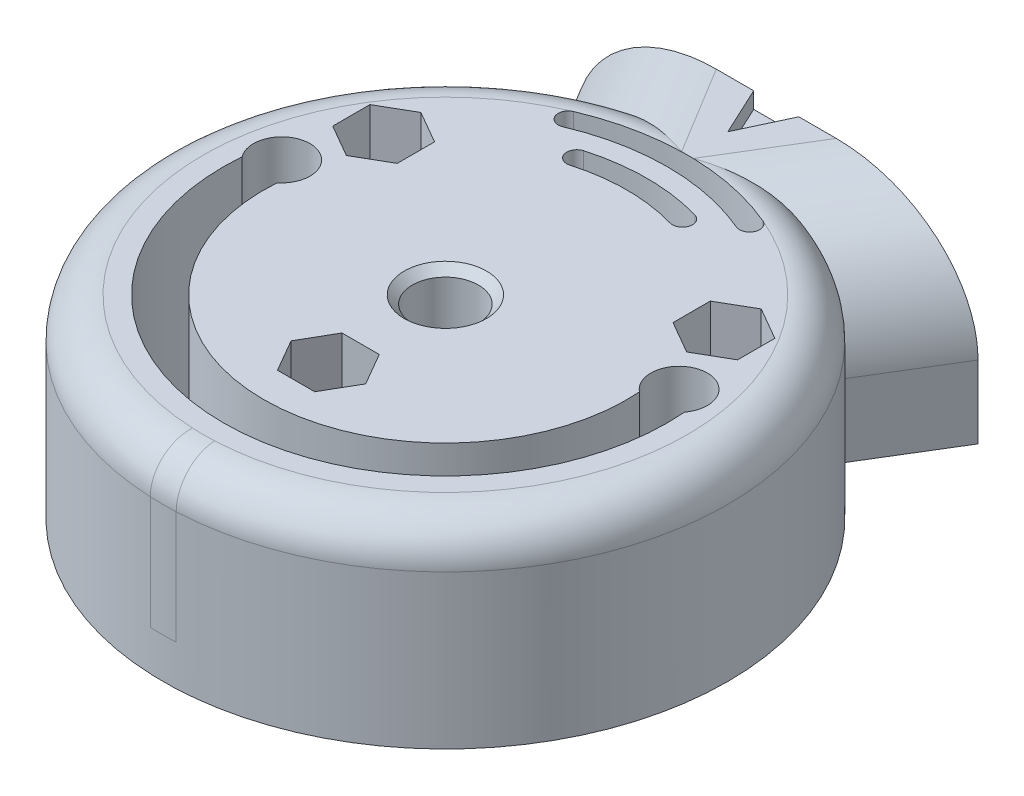
SolidWorks part; units mm, degrees
ref_plane "Alzado" through (0, 0, 0) normal (0, 0, 1) x (1, 0, 0)
ref_plane "Planta" through (0, 0, 0) normal (0, 1, 0) x (1, 0, 0)
ref_plane "Vista lateral" through (0, 0, 0) normal (1, 0, 0) x (0, 0, -1)
sketch "Croquis1" plane through (0, 0, 0) normal (0, 1, 0) x (1, 0, 0)
  line L0 (0, 35) -> (0, 41) construction
  line L1 (-35, 0) -> (-35, 35) construction
  line L2 (35, 0) -> (35, 35) construction
  line L3 (-35, 35) -> (35, 35) construction
  line L4 (0, 38) -> (-35, 38) construction
  line L5 (-35, 38) -> (35, 38) construction
  line L6 (35, 38) -> (35, 35) construction
  line L7 (-35, 38) -> (-35, 35) construction
  line L8 (0, 41) -> (-35, 41) construction
  line L9 (-35, 41) -> (-35, 38) construction
  line L10 (-25, 41) -> (25, 41)
  line L11 (-25, 41) -> (-18.2213, 29.8829)
  line L12 (25, 41) -> (18.2213, 29.8829)
  circle A0 centre (0, 0) radius 35
  circle A1 centre (0, 0) radius 4.1
  point P3 (0, 35)
  dimension "D1" = 70
  dimension "D4" = 8.2
  dimension "D2" = 6
  dimension "D3" = 50
  dimension "D5" = 11.1171
extrude "Saliente-Extruir1" add sketch "Croquis1" along normal blind 24 contours A0 | A0 L10 region at (0, 0, -37.0825) region at (0, 0, -34.0101)
sketch "Croquis2" plane through (0, 24, 0) normal (0, 1, 0) x (1, 0, 0)
  line L0 (0, 41) -> (0, -35) construction
  line L1 (-25, 41) -> (25, 41) construction
  line L2 (0, -33.75) -> (1.05, -33.75)
  line L3 (0, -33.75) -> (-1.05, -33.75)
  line L4 (-1.05, -33.75) -> (-1.55, -33.75) construction
  line L5 (1.05, -33.75) -> (1.55, -33.75) construction
  line L6 (-1.55, -33.75) -> (-1.6057, -34.9631) construction
  line L7 (1.55, -33.75) -> (1.6057, -34.9631) construction
  line L8 (-1.05, -33.75) -> (-1.6057, -34.9631)
  line L9 (1.05, -33.75) -> (1.6057, -34.9631)
  line L10 (-1.6057, -34.9631) -> (-3.3557, -34.8828) construction
  arc A0 (-18.2213, 29.8829) -> (18.2213, 29.8829) centre (0, 0) ccw construction
  circle A1 centre (0, 0) radius 33.75
  circle A2 centre (0, 0) radius 35
  arc M1 (-18.2213, 29.8829) -> (18.2213, 29.8829) centre (0, 0) ccw
  dimension "D1" = 1.25
  dimension "D2" = 2.1
  dimension "D3" = 0.5
  dimension "D4" = 0.5
  dimension "D5" = 1.75
extrude "Cortar-Extruir1" cut sketch "Croquis2" against normal blind 19 contours L9 L2 L3 L8 M1 region at (0, 24, 34.4127)
sketch "Croquis12" plane through (0, 0, -41) normal (0, 0, -1) x (-1, 0, 0)
  line L0 (0, 24) -> (0, 0) construction
  line L1 (25, 24) -> (-25, 24) construction
  line L3 (0, 12) -> (15, 12)
  line L7 (0, 12) -> (-15, 12)
  circle A0 centre (-15, 12) radius 1.65
  circle A1 centre (15, 12) radius 1.65
  dimension "D3" = 3.3
  dimension "D1" = 30
  dimension "D2" = 12
sketch "Croquis13" plane through (0, 0, 0) normal (0, -1, 0) x (1, 0, 0)
  line L0 (25, -41) -> (15, -41) construction
  line L1 (-25, -41) -> (25, -41) construction
  line L2 (15, -41) -> (15, -35) construction
  line L3 (15, -35) -> (11.6, -35) construction
  line L4 (15, -35) -> (18.4, -35) construction
  line L5 (18.4, -35) -> (11.6, -35)
  line L6 (18.4, -35) -> (18.4, -32.1)
  line L7 (18.4, -32.1) -> (11.6, -32.1)
  line L8 (11.6, -32.1) -> (11.6, -35)
  line L9 (0, -41) -> (0, 0) construction
  line L10 (-15, -35) -> (-18.4, -35) construction
  line L11 (-15, -35) -> (-11.6, -35) construction
  line L12 (-11.6, -32.1) -> (-11.6, -35)
  line L13 (-18.4, -32.1) -> (-11.6, -32.1)
  line L14 (-18.4, -35) -> (-18.4, -32.1)
  line L15 (-18.4, -35) -> (-11.6, -35)
  dimension "D1" = 10
  dimension "D2" = 6
  dimension "D3" = 6.8
  dimension "D4" = 2.9
sketch "Croquis8" plane through (0, 24, 0) normal (0, 1, 0) x (1, 0, 0)
  line L0 (0, 0) -> (0, 41) construction
  line L1 (0, 0) -> (-18.4123, 30.6439)
  line L2 (0, 0) -> (18.4123, 30.6439)
  line L9 (-1.6057, -34.9631) -> (-1.05, -33.75)
  line L10 (-1.6057, -34.9631) -> (-1.05, -33.75)
  line L11 (-1.05, -33.75) -> (1.05, -33.75)
  line L12 (-1.05, -33.75) -> (1.05, -33.75)
  line L13 (1.05, -33.75) -> (1.6057, -34.9631)
  line L14 (1.05, -33.75) -> (1.6057, -34.9631)
  line L15 (18.2213, 29.8829) -> (25, 41)
  line L16 (18.2213, 29.8829) -> (25, 41)
  line L17 (25, 41) -> (-25, 41)
  line L18 (25, 41) -> (-25, 41)
  line L19 (-25, 41) -> (-18.2213, 29.8829)
  line L20 (-25, 41) -> (-18.2213, 29.8829)
  circle A0 centre (0, 0) radius 35.75
  circle A1 centre (0, 0) radius 33.25
  arc A3 (-18.2213, 29.8829) -> (-1.6057, -34.9631) centre (0, 0) ccw
  arc A4 (-18.2213, 29.8829) -> (-1.6057, -34.9631) centre (0, 0) ccw
  arc A6 (1.6057, -34.9631) -> (18.2213, 29.8829) centre (0, 0) ccw
  arc A7 (1.6057, -34.9631) -> (18.2213, 29.8829) centre (0, 0) ccw
  dimension "D1" = 71.5
  dimension "D2" = 66.5
  dimension "D4" = 30.6439
  dimension "D3" = 0
extrude "Saliente-Extruir3" add sketch "Croquis8" against normal up to surface (24 mm away) contours A1 L0 A0 L1 | L0 A1 L2 A0 region at (-9.1115, 24, -32.8557) region at (9.1115, 24, -32.8557) up to face at (0, 0, 4.1)
fillet "Redondeo7" radius 15 2 edges at (21.6106, 24, -35.4414) (-21.6106, 24, -35.4414)
sketch "Croquis10" plane through (0, 24, 0) normal (0, 1, 0) x (1, 0, 0)
  line L0 (0, 41) -> (0, -35) construction
  line L1 (-7.4314, 41) -> (7.4314, 41) construction
  line L2 (0, 0) -> (-10.7451, 25.3139) construction
  line L3 (-10.7451, 25.3139) -> (-11.7219, 27.6151) construction
  line L4 (10.7451, 25.3139) -> (11.7219, 27.6151) construction
  line L5 (-8.7915, 20.7114) -> (-9.7683, 23.0126) construction
  line L6 (-8.7915, 20.7114) -> (-9.7683, 23.0126) construction
  line L7 (-8.7915, 20.7114) -> (-9.7683, 23.0126)
  line L8 (0, 0) -> (6.1996, 21.629) construction
  line L9 (6.1996, 21.629) -> (6.8885, 24.0323) construction
  line L10 (-6.1996, 21.629) -> (-6.8885, 24.0323) construction
  circle A0 centre (0, 0) radius 30
  circle A1 centre (0, 0) radius 27.5
  arc A2 (-1.6057, -34.9631) -> (1.6057, -34.9631) centre (0, 0) ccw construction
  arc A3 (-11.7219, 27.6151) -> (-10.7451, 25.3139) centre (-11.2335, 26.4645) ccw
  arc A4 (11.7219, 27.6151) -> (10.7451, 25.3139) centre (11.2335, 26.4645) cw
  circle A5 centre (0, 0) radius 25
  circle A6 centre (0, 0) radius 22.5
  arc A7 (6.1996, 21.629) -> (6.8885, 24.0323) centre (6.544, 22.8306) ccw
  arc A8 (-6.1996, 21.629) -> (-6.8885, 24.0323) centre (-6.544, 22.8306) cw
  point P19 (-8.7915, 20.7114)
  dimension "D1" = 60
  dimension "D2" = 55
  dimension "D4" = 50
  dimension "D5" = 45
  dimension "D3" = 23
extrude "Cortar-Extruir5" cut sketch "Croquis10" against normal blind 29 contours A4 A0 A3 A1 | A8 A6 A7 A5 region at (0, 24, -23.3638) region at (0, 24, -27.8649)
sketch "Croquis11" plane through (0, 24, 0) normal (0, 1, 0) x (1, 0, 0)
  line L0 (-21.1734, 3.7334) -> (-22.1582, 3.9071) construction
  line L2 (0, 0) -> (0, -35) construction
  arc A0 (-27.4097, 2.2272) -> (27.4097, 2.2272) centre (0, 0) ccw
  arc A1 (-22.443, 1.6008) -> (22.443, 1.6008) centre (0, 0) ccw
  arc A2 (-1.6057, -34.9631) -> (1.6057, -34.9631) centre (0, 0) ccw construction
  arc A3 (-22.443, 1.6008) -> (-27.4097, 2.2272) centre (-24.6202, 4.3412) ccw
  arc A4 (22.443, 1.6008) -> (27.4097, 2.2272) centre (24.6202, 4.3412) cw
  dimension "D1" = 55
  dimension "D2" = 45
  dimension "D4" = 7
  dimension "D3" = 100
extrude "Cortar-Extruir6" cut sketch "Croquis11" against normal blind 29
extrude "Cortar-Extruir11" cut sketch "Croquis13" against normal blind 12
sketch "Croquis15" plane through (0, 0, -32.1) normal (0, 0, -1) x (-1, 0, 0)
  line L0 (-18.4, 12) -> (-11.6, 12) construction
  line L1 (-15, 8.5359) -> (-12, 10.2679)
  line L2 (-12, 10.2679) -> (-12, 13.7321)
  line L3 (-12, 13.7321) -> (-15, 15.4641)
  line L4 (-15, 15.4641) -> (-18, 13.7321)
  line L5 (-18, 13.7321) -> (-18, 10.2679)
  line L6 (-18, 10.2679) -> (-15, 8.5359)
  line L7 (0, 24) -> (0, 0) construction
  line L8 (-11.7219, 0) -> (11.7219, 0) construction
  line L9 (18, 10.2679) -> (15, 8.5359)
  line L10 (18, 13.7321) -> (18, 10.2679)
  line L11 (15, 15.4641) -> (18, 13.7321)
  line L12 (12, 13.7321) -> (15, 15.4641)
  line L13 (12, 10.2679) -> (12, 13.7321)
  line L14 (15, 8.5359) -> (12, 10.2679)
  circle A0 centre (-15, 12) radius 3 construction
  circle A1 centre (15, 12) radius 3 construction
  dimension "D1" = 6
extrude "Cortar-Extruir13" cut sketch "Croquis15" along normal blind 2.7
extrude "Cortar-Extruir14" cut sketch "Croquis12" against normal blind 15 contours A0 | A1 region at (-15, 13.6033, -41) region at (16.6033, 12, -41)
chamfer "Chaflán1" distance 1 angle 45 1 edges at (0, 24, 4.1)
chamfer "Chaflán2" distance 1 angle 45 1 edges at (0, 0, 4.1)
sketch "Croquis16" plane through (0, 5, 0) normal (0, 1, 0) x (1, 0, 0)
  line L0 (-1.05, -33.75) -> (1.05, -33.75)
  line L1 (1.05, -33.75) -> (1.6057, -34.9631)
  line L2 (-1.05, -33.75) -> (-1.6057, -34.9631)
  arc A0 (-1.6057, -34.9631) -> (1.6057, -34.9631) centre (0, 0) ccw construction
  spline S0 degree 2 poles (-1.6057, -34.9631) (0, -35.0369) (1.6057, -34.9631) knots 0 0 0 1 1 1
extrude "Saliente-Extruir4" add sketch "Croquis16" along normal up to surface (19 mm away) up to face at (0, 24, 5.1)
fillet "Redondeo18" radius 5 3 edges at (34.9849, 24, 1.0281) (-34.9849, 24, 1.0281)
sketch "Croquis17" plane through (0, 24, 0) normal (0, 1, 0) x (1, 0, 0)
  line L0 (0, 25) -> (0, 0) construction
  line L1 (0, 0) -> (21.0848, 13.4325) construction
  line L2 (0, 0) -> (0, -25) construction
  circle A0 centre (0, 0) radius 25 construction
  circle A1 centre (21.0848, 13.4325) radius 2.15
  circle A3 centre (0, -14.5) radius 2.15
  circle A4 centre (-21.0848, 13.4325) radius 2.15
  dimension "D1" = 50
  dimension "D3" = 4.3
  dimension "D2" = 122.5
  dimension "D4" = 14.5
extrude "Cortar-Extruir15" cut sketch "Croquis17" against normal blind 40 contours A3 | A4 A0 | A4 A0 | A0 A1 | A0 A1 region at (21.0848, 24, -13.4325) region at (0, 24, 14.5) region at (-21.0848, 24, -13.4325)
sketch "Croquis18" plane through (0, 24, 0) normal (0, 1, 0) x (1, 0, 0)
  line L0 (-21.0848, 18.0513) -> (-21.0848, 8.8137) construction
  line L1 (-21.0848, 18.0513) -> (-25.0848, 15.7419)
  line L2 (-25.0848, 15.7419) -> (-25.0848, 11.1231)
  line L3 (-25.0848, 11.1231) -> (-21.0848, 8.8137)
  line L4 (-21.0848, 8.8137) -> (-17.0848, 11.1231)
  line L5 (-17.0848, 11.1231) -> (-17.0848, 15.7419)
  line L6 (-17.0848, 15.7419) -> (-21.0848, 18.0513)
  line L7 (0, -10.5) -> (0, -18.5) construction
  line L8 (4.6188, -14.5) -> (2.3094, -10.5)
  line L9 (2.3094, -10.5) -> (-2.3094, -10.5)
  line L10 (-2.3094, -10.5) -> (-4.6188, -14.5)
  line L11 (-4.6188, -14.5) -> (-2.3094, -18.5)
  line L12 (-2.3094, -18.5) -> (2.3094, -18.5)
  line L13 (2.3094, -18.5) -> (4.6188, -14.5)
  line L14 (21.0848, 18.0513) -> (21.0848, 8.8137) construction
  line L15 (21.0848, 18.0513) -> (17.0848, 15.7419)
  line L16 (17.0848, 15.7419) -> (17.0848, 11.1231)
  line L17 (17.0848, 11.1231) -> (21.0848, 8.8137)
  line L18 (21.0848, 8.8137) -> (25.0848, 11.1231)
  line L19 (25.0848, 11.1231) -> (25.0848, 15.7419)
  line L20 (25.0848, 15.7419) -> (21.0848, 18.0513)
  circle A0 centre (-21.0848, 13.4325) radius 4 construction
  circle A1 centre (0, -14.5) radius 4 construction
  circle A2 centre (21.0848, 13.4325) radius 4 construction
  dimension "D1" = 8
extrude "Cortar-Extruir16" cut sketch "Croquis18" against normal blind 14
sketch "Croquis19" plane through (0, 24, 0) normal (0, 1, 0) x (1, 0, 0)
  line L0 (0, 41) -> (0, 30) construction
  line L1 (-7.4314, 41) -> (7.4314, 41) construction
  line L2 (0, 35) -> (-2.7978, 41)
  line L3 (0, 35) -> (2.7978, 41)
  line L4 (-2.7978, 41) -> (2.7978, 41)
  arc A0 (0.7188, 29.9914) -> (-0.7188, 29.9914) centre (0, 0) ccw construction
  dimension "D1" = 6
  dimension "D3" = 25
extrude "Cortar-Extruir17" cut sketch "Croquis19" against normal blind 2
